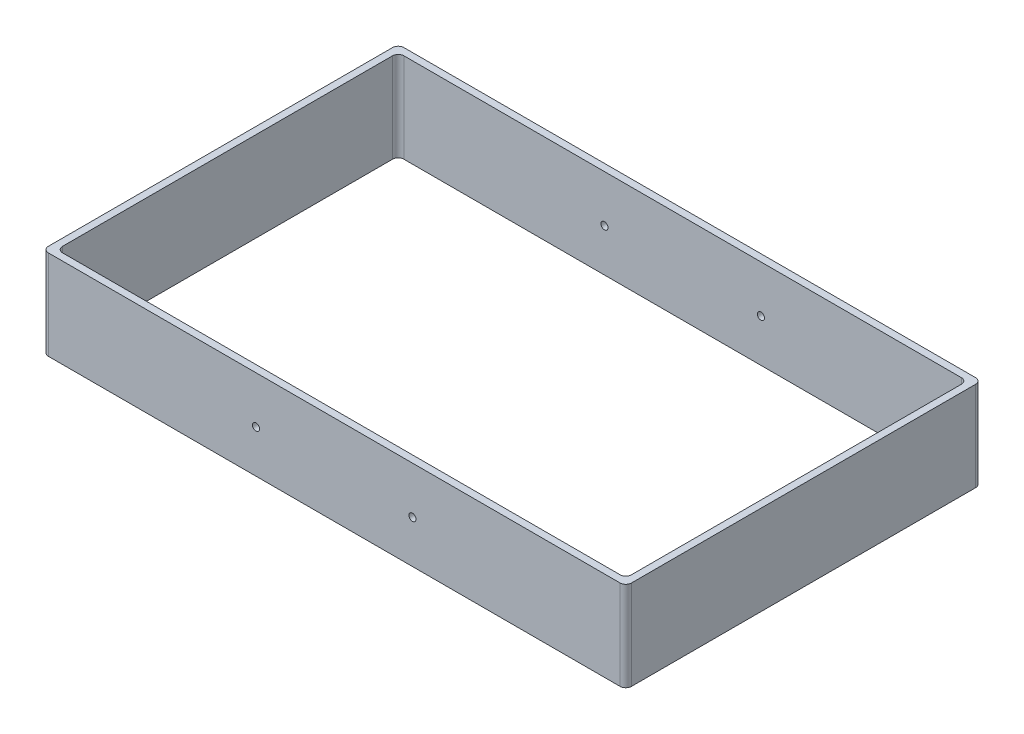
SolidWorks part; units mm, degrees
ref_plane "Front Plane" through (0, 0, 0) normal (0, 0, 1) x (1, 0, 0)
ref_plane "Top Plane" through (0, 0, 0) normal (0, 1, 0) x (1, 0, 0)
ref_plane "Right Plane" through (0, 0, 0) normal (1, 0, 0) x (0, 0, -1)
sketch "Sketch2" plane through (0, 0, 0) normal (0, 1, 0) x (1, 0, 0)
  line L1 (-72.0725, 0) -> (-72.0725, 158.75)
  line L4 (-75.2475, -3.175) -> (-75.2475, 161.925)
  line L19 (53.2587, 0) -> (53.2587, -3.175)
  line L20 (-72.0725, 158.75) -> (0, 158.75) construction
  line L21 (0, 0) -> (-72.0725, 0) construction
  line L25 (-75.2475, -3.175) -> (53.2587, -3.175)
  line L26 (0, -3.175) -> (-75.2475, -3.175) construction
  line L27 (-72.0725, 0) -> (53.2587, 0)
  line L28 (-75.2475, 161.925) -> (16.1925, 161.925)
  line L29 (-75.2475, 161.925) -> (0, 161.925) construction
  line L30 (-72.0725, 158.75) -> (16.1925, 158.75)
  line L35 (16.1925, 161.925) -> (53.2587, 161.925)
  line L36 (53.2587, 161.925) -> (53.2587, 158.75)
  line L37 (53.2587, 158.75) -> (16.1925, 158.75)
  dimension "D7" = 75.2475
  dimension "D1" = 128.5062
  dimension "D2" = 158.75
  dimension "D3" = 3.175
  dimension "D5" = 3.175
  dimension "D6" = 128.5062
  dimension "D8" = 158.75
  dimension "D4" = 3.175
ref_plane "Plane1" through (0, -38.1, 0) normal (0, 1, 0) x (1, 0, 0)
sketch "Sketch4" plane through (0, 0, 0) normal (0, 1, 0) x (1, 0, 0)
  line L14 (-3.175, -3.175) -> (-3.175, 155.575)
  line L15 (0, 0) -> (254, 0)
  line L16 (0, 0) -> (0, 152.4)
  line L17 (0, 152.4) -> (254, 152.4)
  line L18 (254, 0) -> (254, 152.4)
  line L19 (-3.175, 155.575) -> (257.175, 155.575)
  line L20 (257.175, -3.175) -> (257.175, 155.575)
  line L21 (-3.175, -3.175) -> (257.175, -3.175)
  dimension "D1" = 152.4
  dimension "D2" = 254
  dimension "D3" = 3.175
extrude "Boss-Extrude1" add sketch "Sketch4" along normal blind 38.1 contours L20 L19 L14 L21 | L17 L18 L15 L16
sketch "Sketch5" plane through (0, 0, 3.175) normal (0, 0, 1) x (1, 0, 0)
  line L0 (-3.175, 38.1) -> (-3.175, 0) construction
  line L1 (-3.175, 0) -> (257.175, 0) construction
  line L2 (-3.175, 38.1) -> (257.175, 38.1) construction
  circle A0 centre (92.075, 19.05) radius 1.5875
  circle A1 centre (161.925, 19.05) radius 1.5875
  point P0 (60.325, 19.05)
  point P1 (161.925, 19.05)
  point P2 (92.075, 19.05)
  point P3 (193.675, 19.05)
  point P4 (127, 19.05)
  dimension "D11" = 3.175
  dimension "D12" = 3.175
  dimension "D1" = 130.175
  dimension "D2" = 19.05
  dimension "D3" = 66.675
  dimension "D4" = 19.05
  dimension "D5" = 66.675
  dimension "D6" = 19.05
  dimension "D7" = 31.75
  dimension "D8" = 31.75
  dimension "D9" = 19.05
  dimension "D10" = 19.05
extrude "Cut-Extrude1" cut sketch "Sketch5" against normal through all contours A0
extrude "Cut-Extrude2" cut sketch "Sketch5<4>" against normal through all contours A1
sketch "Sketch5<4>" plane through (0, 0, 3.175) normal (0, 0, 1) x (1, 0, 0) same geometry as "Sketch5"
sketch "Sketch8" plane through (0, 38.1, 0) normal (0, 1, 0) x (1, 0, 0)
  line L0 (-3.175, 155.575) -> (257.175, 155.575)
  line L1 (257.175, 155.575) -> (257.175, -3.175)
  line L2 (257.175, -3.175) -> (-3.175, -3.175)
  line L3 (-3.175, -3.175) -> (-3.175, 155.575)
  line L4 (0, 152.4) -> (254, 152.4)
  line L5 (254, 152.4) -> (254, 0)
  line L6 (254, 0) -> (0, 0)
  line L7 (0, 0) -> (0, 152.4)
extrude "Boss-Extrude2" add sketch "Sketch8" along normal blind 1.905
fillet "Fillet1" radius 2.54 4 edges at (254, 20.0025, 0) (0, 20.0025, 0) (254, 20.0025, -152.4) (0, 20.0025, -152.4)
fillet "Fillet2" radius 2.54 4 edges at (-3.175, 20.0025, 3.175) (-3.175, 20.0025, -155.575) (257.175, 20.0025, -155.575) (257.175, 20.0025, 3.175)
